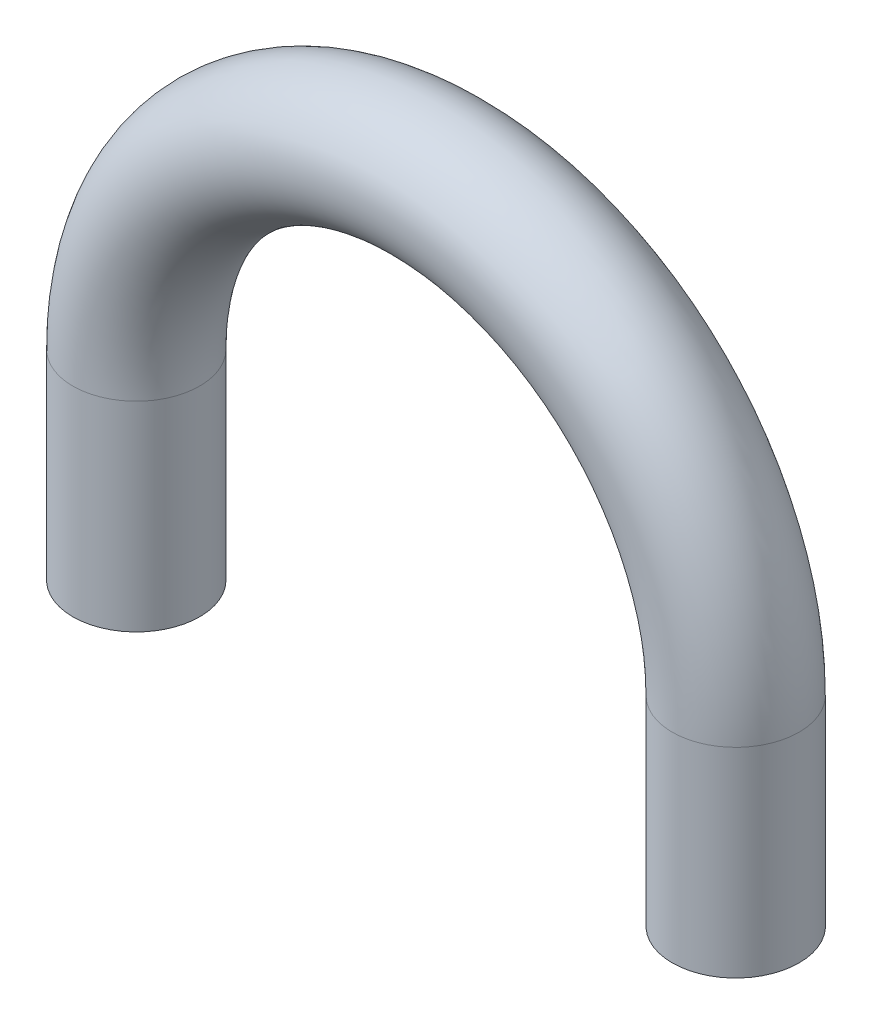
SolidWorks part; units mm, degrees
ref_plane "Plan de face" through (0, 0, 0) normal (0, 0, 1) x (1, 0, 0)
ref_plane "Plan de dessus" through (0, 0, 0) normal (0, 1, 0) x (1, 0, 0)
ref_plane "Plan de droite" through (0, 0, 0) normal (1, 0, 0) x (0, 0, -1)
sketch "Esquisse1" plane through (0, 0, 0) normal (0, 0, 1) x (1, 0, 0)
  line L0 (-15, -10) -> (-15, 0)
  line L1 (15, -10) -> (15, 0)
  arc A0 (-15, 0) -> (15, 0) centre (0, 0) cw
sweep "Balayage3" add path "Esquisse1" circular profile diameter 6.35 parameters "D3"=6.35
